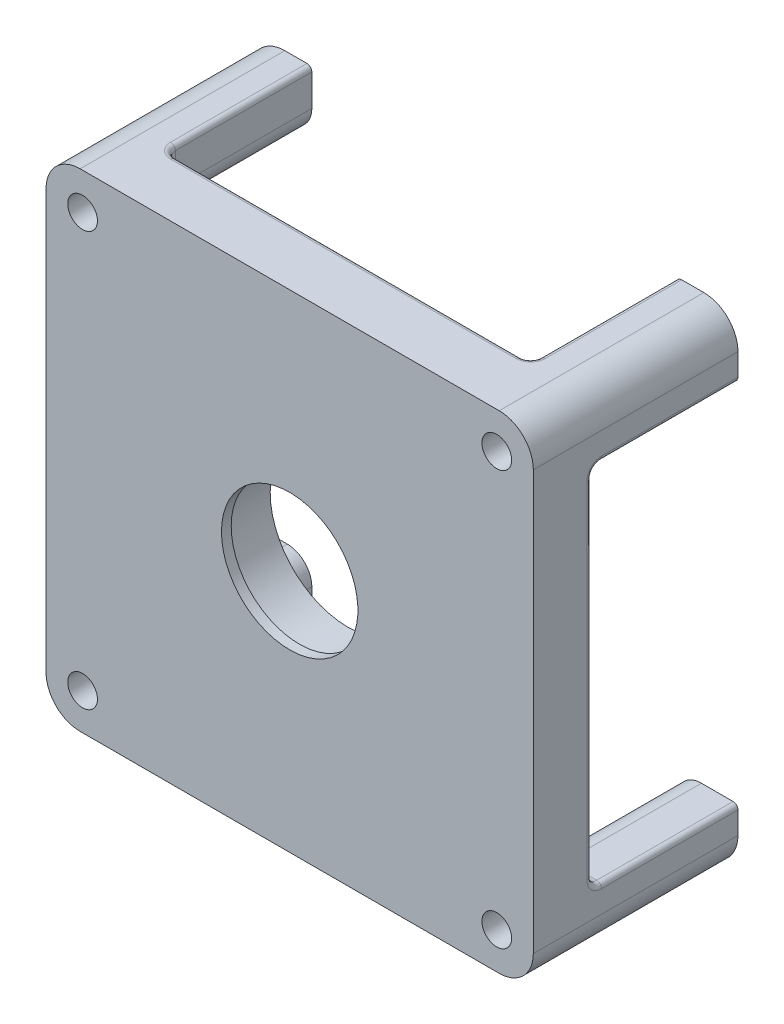
SolidWorks part; units mm, degrees
note: '?' marks a value the reader was unsure of.
ref_plane "Front Plane" through (0, 0, 0) normal (0, 0, 1) x (1, 0, 0)
ref_plane "Top Plane" through (0, 0, 0) normal (0, 1, 0) x (1, 0, 0)
ref_plane "Right Plane" through (0, 0, 0) normal (1, 0, 0) x (0, 0, -1)
ref_axis "Shaft Axis" through (0, 0, -0.635) along (0, 0, 1)?
sketch "Sketch2" plane through (0, 0, 0) normal (0, 0, 1) x (1, 0, 0)
  line L1 (-50, -50) -> (50, -50)
  line L2 (-50, -50) -> (-50, 50)
  line L3 (-50, 50) -> (50, 50)
  line L4 (50, -50) -> (50, 50)
  line L5 (-50, -50) -> (50, 50) construction
  line L6 (-50, 50) -> (50, -50) construction
  point P0 (0, 0)
  dimension "D1" = 100
extrude "Boss-Extrude1" add sketch "Sketch2" along normal blind 12
sketch "Sketch3" plane through (0, 0, 0) normal (0, 0, -1) x (-1, 0, 0)
  circle A0 centre (0, 0) radius 16
  dimension "D1" = 32
extrude "Cut-Extrude1" cut sketch "Sketch3" against normal blind 10
sketch "Sketch14" plane through (0, 0, 12) normal (0, 0, 1) x (1, 0, 0)
  circle A0 centre (0, 0) radius 65
  dimension "D1" = 130
extrude "Cut-Extrude2" [suppressed] cut sketch "Sketch14" against normal blind 2 flip side to cut
hole_wizard "7/16 Clearance Hole1" [suppressed] positions "Sketch7" profile "Sketch8" hole size "7/16" standard "ANSI Inch"
sketch "Sketch7" [suppressed] plane through (0, 0, 10.7) normal (0, 0, 1) x (1, 0, 0)
  line L1 (-58.7375, -58.7375) -> (58.7375, -58.7375) construction
  line L2 (-58.7375, -58.7375) -> (-58.7375, 58.7375) construction
  line L3 (-58.7375, 58.7375) -> (58.7375, 58.7375) construction
  line L4 (58.7375, -58.7375) -> (58.7375, 58.7375) construction
  line L5 (-58.7375, -58.7375) -> (58.7375, 58.7375) construction
  line L6 (-58.7375, 58.7375) -> (58.7375, -58.7375) construction
  line L7 (-76.2, 76.2) -> (76.2, -76.2) construction
  line L8 (76.2, -76.2) -> (76.2, 76.2) construction
  line L9 (76.2, 76.2) -> (-76.2, -76.2) construction
  point P2 (58.7375, 58.7375)
  point P35 (-58.7375, -58.7375)
  point P36 (-58.7375, 58.7375)
  point P37 (58.7375, -58.7375)
  dimension "D1" = 117.475
sketch "Sketch8" plane through (58.7375, 58.7375, 10.7) normal (1, 0, 0) x (0, -1, 0)
  line L0 (0, 0) -> (0, 10.7)
  line L1 (0, 10.7) -> (6.1519, 10.7)
  line L2 (6.1519, 10.7) -> (6.1519, 0)
  line L5 (6.1519, 0) -> (0, 0)
  line L11 (0, -6.35) -> (0, 107.95) construction
  dimension "Thru Hole Dia." = 12.3038
  dimension "Thru Hole Depth" = 10.7
hole_wizard "M6 Clearance Hole1" positions "Sketch13" profile "Sketch12" hole size "M6" standard "ANSI Metric" end condition through all
sketch "Sketch13" plane through (0, 0, 12) normal (0, 0, -1) x (-1, 0, 0)
  line L1 (-42.5, -42.5) -> (42.5, -42.5) construction
  line L2 (-42.5, -42.5) -> (-42.5, 42.5) construction
  line L3 (-42.5, 42.5) -> (42.5, 42.5) construction
  line L4 (42.5, -42.5) -> (42.5, 42.5) construction
  line L5 (-42.5, -42.5) -> (42.5, 42.5) construction
  line L6 (-42.5, 42.5) -> (42.5, -42.5) construction
  line L22 (50, -50) -> (50, 50)
  line L24 (50, 50) -> (-50, -50) construction
  line L26 (-50, 50) -> (50, -50) construction
  line L43 (-50, 50) -> (-50, -50)
  line L44 (-50, 50) -> (-50, -50)
  line L45 (50, 50) -> (-50, 50)
  line L46 (50, 50) -> (-50, 50)
  line L47 (50, -50) -> (50, 50)
  line L48 (50, -50) -> (50, 50)
  line L49 (-50, -50) -> (50, -50)
  line L50 (-50, -50) -> (50, -50)
  point P2 (42.5, 42.5)
  point P61 (-42.5, -42.5)
  point P62 (-42.5, 42.5)
  point P63 (42.5, -42.5)
  dimension "D1" = 85
  dimension "D2" = 0
sketch "Sketch12" plane through (-42.5, 42.5, 12) normal (1, 0, 0) x (0, -1, 0)
  line L0 (0, 0) -> (0, 12)
  line L1 (0, 12) -> (3.05, 12)
  line L2 (3.05, 12) -> (3.05, 0)
  line L5 (3.05, 0) -> (0, 0)
  line L11 (0, -6.35) -> (0, 107.95) construction
  dimension "Thru Hole Dia." = 6.1
  dimension "Thru Hole Depth" = 12
sketch "Sketch17" plane through (0, 0, 0) normal (0, 0, -1) x (-1, 0, 0)
  line L0 (-37.45, 42.5) -> (-37.45, 50)
  line L1 (-50, 50) -> (50, 50) construction
  line L2 (-37.45, 50) -> (-50, 50)
  line L3 (-50, 50) -> (-50, 37.45)
  line L4 (-50, -50) -> (-50, 50) construction
  line L5 (-42.5, 37.45) -> (-50, 37.45)
  arc A0 (-42.5, 37.45) -> (-37.45, 42.5) centre (-42.5, 42.5) ccw
  circle A1 centre (-42.5, 42.5) radius 3.05 construction
  circle A2 centre (-42.5, 42.5) radius 3.05
  point P12 (-50, 50)
  point P16 (-37.3, 50)
  point P17 (-50, 48.3991)
  point P18 (-50, 50)
  dimension "D1" = 2
extrude "Boss-Extrude2" add sketch "Sketch17" along normal blind 30
pattern_circular "CirPattern1" count 4 over 360 about axis through (0, 0, 0) along (0, 0, 1) of "Boss-Extrude2"
sketch "Sketch18" plane through (0, 0, 0) normal (0, 0, -1) x (-1, 0, 0)
  circle A0 centre (0, 0) radius 14
  dimension "D1" = 28
extrude "Cut-Extrude3" cut sketch "Sketch18" against normal through all
fillet "Fillet1" radius 2 12 edges at (38.9291, 38.9291, 0) (-38.9291, 38.9291, 0) (-38.9291, -38.9291, 0) (38.9291, -38.9291, 0) (-37.45, 46.25, 0) (-46.25, 37.45, 0) (-46.25, -37.45, 0) (-37.45, -46.25, 0) (37.45, -46.25, 0) (46.25, -37.45, 0) (46.25, 37.45, 0) (37.45, 46.25, 0)
fillet "Fillet2" radius 7 4 edges at (-50, -50, -9) (50, -50, -9) (50, 50, -9) (-50, 50, -9)
sketch "Sketch24" [suppressed] plane through (0, 0, 12) normal (0, 0, 1) x (1, 0, 0)
  line L1 (-44.4006, 48.0738) -> (-48.2774, 43.6409)
  line L2 (-48.2774, 43.6409) -> (-46.3768, 38.0671)
  line L3 (-46.3768, 38.0671) -> (-40.5994, 36.9262)
  line L4 (-40.5994, 36.9262) -> (-36.7226, 41.3591)
  line L5 (-36.7226, 41.3591) -> (-38.6232, 46.9329)
  line L6 (-38.6232, 46.9329) -> (-44.4006, 48.0738)
  circle A0 centre (-42.5, 42.5) radius 5.1 construction
  dimension "D1" = 10.2
extrude "Cut-Extrude6" [suppressed] cut sketch "Sketch24" against normal blind 4
pattern_circular "CirPattern2" [suppressed] count 4 over 360 about axis through (0, 0, -0.635) along (0, 0, 1)
fillet "Fillet3" radius 1 20 edges at (50, 0, 0) (0, -50, 0) (-50, 0, 0) (0, 50, 0) (-36.8642, 50, -0.5858) (-50, 36.8642, -0.5858) (-50, -36.8642, -0.5858) (-36.8642, -50, -0.5858) (36.8642, -50, -0.5858) (50, -36.8642, -0.5858) (50, 36.8642, -0.5858) (36.8642, 50, -0.5858) (37.45, 50, -16) (50, 37.45, -16) (-50, 37.45, -16) (-37.45, 50, -16) (-37.45, -50, -16) (-50, -37.45, -16) (50, -37.45, -16) (37.45, -50, -16)
